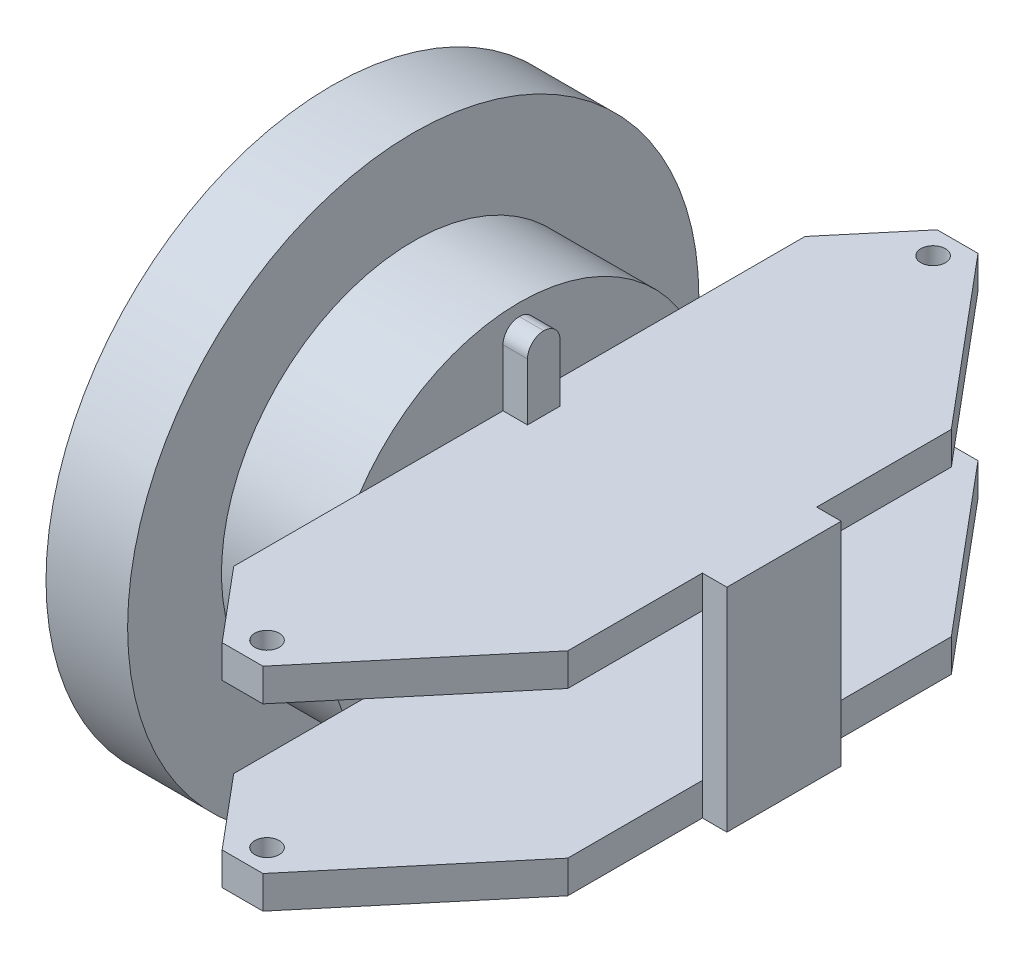
SolidWorks part; units mm, degrees
ref_plane "Front Plane" through (0, 0, 0) normal (0, 0, 1) x (1, 0, 0)
ref_plane "Top Plane" through (0, 0, 0) normal (0, 1, 0) x (1, 0, 0)
ref_plane "Right Plane" through (0, 0, 0) normal (1, 0, 0) x (0, 0, -1)
sketch "Sketch1" plane through (0, 0, 0) normal (1, 0, 0) x (0, 0, -1)
  circle A0 centre (0, 0) radius 35
  dimension "D1" = 70
extrude "Boss-Extrude1" add sketch "Sketch1" along normal blind 10
sketch "Sketch2" plane through (10, 0, 0) normal (1, 0, 0) x (0, 0, -1)
  circle A0 centre (0, 0) radius 23.5
  dimension "D1" = 47
extrude "Boss-Extrude2" add sketch "Sketch2" along normal blind 13
ref_plane "Plane1" through (0, 13, 0) normal (0, 1, 0) x (1, 0, 0)
sketch "Sketch3" plane through (0, 13, 0) normal (0, 1, 0) x (1, 0, 0)
  line L0 (23, 35) -> (23, -35)
  line L1 (23, -23.5) -> (23, 23.5) construction
  line L2 (23, -35) -> (30.3921, -43.8095)
  line L3 (30.3921, -43.8095) -> (35.3921, -43.8095)
  line L4 (35.3921, -43.8095) -> (52.4338, -23.5)
  line L5 (23, -23.5) -> (83.4459, -23.5) construction
  line L6 (52.4338, -23.5) -> (52.4338, 23.5)
  line L7 (23, 0) -> (73.6378, 0) construction
  line L8 (23, 35) -> (30.3921, 43.8095)
  line L9 (30.3921, 43.8095) -> (35.3921, 43.8095)
  line L10 (35.3921, 43.8095) -> (52.4338, 23.5)
  line L11 (10, -23.5) -> (23, -23.5) construction
  point P15 (52.4338, 0)
  dimension "D1" = 35
  dimension "D2" = 40
  dimension "D3" = 11.5
  dimension "D4" = 5
  dimension "D5" = 50
extrude "Boss-Extrude3" add sketch "Sketch3" against normal blind 4
sketch "Sketch4" plane through (0, 13, 0) normal (0, 1, 0) x (1, 0, 0)
  line L0 (30.3921, -43.8095) -> (35.3921, -43.8095) construction
  circle A0 centre (32.8921, -40.8095) radius 1.5
  dimension "D1" = 3
  dimension "D2" = 3
extrude "Cut-Extrude1" cut sketch "Sketch4" against normal blind 4
mirror "Mirror1" about plane through (0, 0, 0) normal (0, 0, 1) of "Cut-Extrude1"
mirror "Mirror2" about plane through (0, 0, 0) normal (0, 1, 0) of "Mirror1", "Cut-Extrude1", "Boss-Extrude3"
sketch "Sketch5" plane through (23, 0, 0) normal (1, 0, 0) x (0, 0, -1)
  line L0 (0, 23.5) -> (0, 13) construction
  line L1 (19.5768, 13) -> (-19.5768, 13) construction
  line L2 (-2, 22) -> (2, 22)
  line L3 (2, 22) -> (2, 13)
  line L4 (2, 13) -> (-2, 13)
  line L5 (-23.5, 13) -> (23.5, 13) construction
  line L6 (-2, 13) -> (-2, 22)
  arc A0 (19.5768, 13) -> (-19.5768, 13) centre (0, 0) ccw construction
  dimension "D1" = 9
  dimension "D2" = 2
  dimension "D3" = 2
extrude "Boss-Extrude4" add sketch "Sketch5" along normal blind 3
fillet "Fillet1" radius 2 2 edges at (24.5, 22, 2) (24.5, 22, -2)
mirror "Mirror3" about plane through (0, 0, 0) normal (0, 1, 0) of "Fillet1", "Boss-Extrude4"
sketch "Sketch6" plane through (52.4338, 0, 0) normal (1, 0, 0) x (0, 0, -1)
  line L1 (-7, -13) -> (7, -13)
  line L2 (-7, -13) -> (-7, 13)
  line L3 (-7, 13) -> (7, 13)
  line L4 (7, -13) -> (7, 13)
  line L5 (-7, -13) -> (7, 13) construction
  line L6 (-7, 13) -> (7, -13) construction
  point P0 (0, 0)
  dimension "D1" = 14
  dimension "D2" = 26
extrude "Boss-Extrude5" add sketch "Sketch6" along normal blind 3
sketch "Sketch7" plane through (0, 0, 0) normal (-1, 0, 0) x (0, 0, 1)
  circle A0 centre (0, 0) radius 10
  dimension "D1" = 20
extrude "Cut-Extrude2" cut sketch "Sketch7" against normal blind 10
